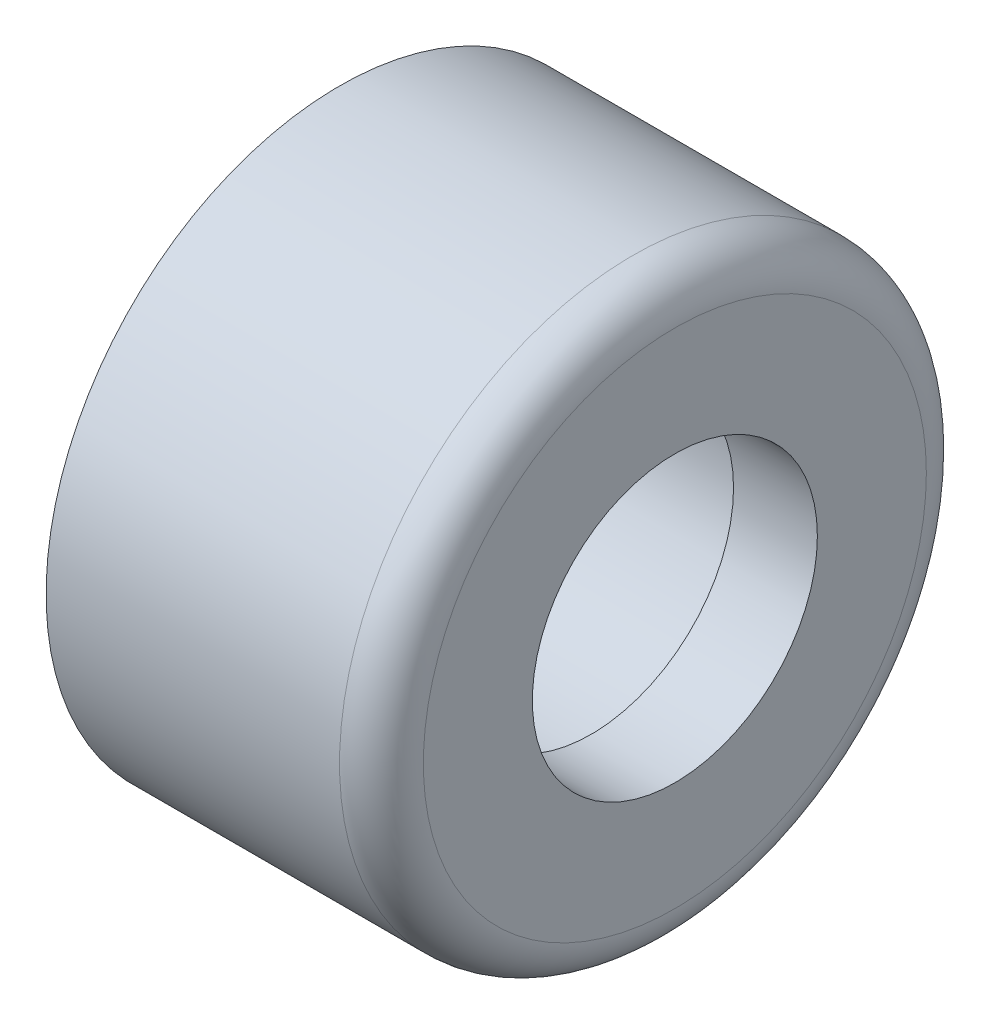
SolidWorks part; units mm, degrees
ref_plane "Front Plane" through (0, 0, 0) normal (0, 0, 1) x (1, 0, 0)
ref_plane "Top Plane" through (0, 0, 0) normal (0, 1, 0) x (1, 0, 0)
ref_plane "Right Plane" through (0, 0, 0) normal (1, 0, 0) x (0, 0, -1)
ref_axis "X-Axis" through (88.99, 0, 0) along (-1, 0, 0)
ref_axis "Y-Axis" through (0, 0, -88.99) along (0, 0, 1)
ref_axis "Z-Axis" through (0, -55, 0) along (0, 1, 0)
sketch "Sketch2" plane through (0, 0, 0) normal (0, 1, 0) x (1, 0, 0)
  line L0 (88.99, 0) -> (-88.99, 0) construction
  line L1 (-8, 14) -> (8, 14)
  line L2 (-8, 14) -> (-8, 8)
  line L3 (-8, 8) -> (4, 8)
  line L6 (4, 8) -> (4, 6.8)
  line L7 (4, 6.8) -> (8, 6.8)
  line L8 (8, 14) -> (8, 6.8)
  line L9 (0, 88.99) -> (0, -88.99) construction
  point P3 (0, 14)
  point P9 (-8, 11)
  dimension "D1" = 8
  dimension "D2" = 1.2
  dimension "D3" = 6
  dimension "D4" = 12
  dimension "D5" = 4
revolve "Revolve1" add sketch "Sketch2" angle 360 about axis through (88.99, 0, 0) along (-1, 0, 0)
sketch "Sketch3" plane through (-8, 0, 0) normal (-1, 0, 0) x (0, 0, 1)
  line L0 (-88.99, 0) -> (88.99, 0) construction
  circle A0 centre (10, 0) radius 1.25
  circle A1 centre (0, 0) radius 14 construction
  dimension "D1" = 2.5
  dimension "D2" = 10
hole_wizard "Tap Drill for M3x0.5 Tap1" positions "3DSketch1" profile "Sketch4" hole size "M3x0.5" standard "ANSI Metric"
sketch3d "3DSketch1"
  point P0 (-8, 0, 10)
sketch "Sketch4" plane through (-8, 0, 10) normal (0, 1, 0) x (0, 0, 1)
  line L0 (0, 0) -> (0, 8.7511)
  line L1 (0, 8.7511) -> (1.25, 8)
  line L2 (1.25, 8) -> (1.25, 0)
  line L5 (1.25, 0) -> (0, 0)
  line L10 (0, 8.7511) -> (-1.25, 8) construction
  line L11 (0, -6.35) -> (0, 107.95) construction
  dimension "Hole Dia." = 2.5
  dimension "Hole Depth" = 8
  dimension "Drill Angle" = 118
pattern_circular "CirPattern1" count 4 over 360 about axis through (88.99, 0, 0) along (-1, 0, 0) of "Tap Drill for M3x0.5 Tap1" reverse direction yes
fillet "Fillet1" radius 2 1 edges at (8, 0, -14)
